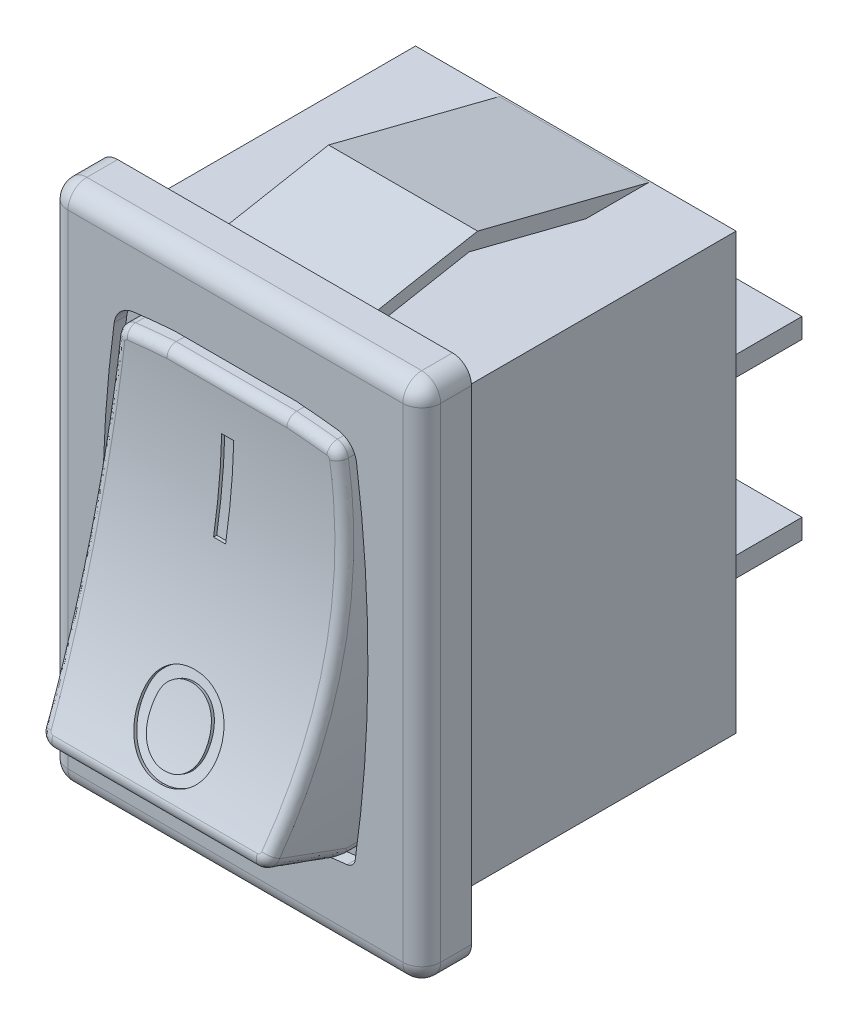
SolidWorks part; units mm, degrees
material "PW100:Mi:0:30:C1:0:1:2:Re:16:"
ref_plane "Plane1" through (0, 0, 0) normal (0, 0, 1) x (1, 0, 0)
ref_plane "Plane2" through (0, 0, 0) normal (0, 1, 0) x (1, 0, 0)
ref_plane "Plane3" through (0, 0, 0) normal (1, 0, 0) x (0, 0, -1)
sketch "Sketch1" plane through (0, 0, 0) normal (0, 0, 1) x (1, 0, 0)
  line L4 (-7.5, 10.5) -> (7.5, 10.5)
  line L5 (-7.5, 10.5) -> (-7.5, -10.5)
  line L6 (7.5, -10.5) -> (-7.5, -10.5)
  line L7 (7.5, -10.5) -> (7.5, 10.5)
  point P0 (0, 10.5)
  dimension "D1" = 15
  dimension "D2" = 21
  dimension "D3" = 7.5
  dimension "D4" = 10.5
extrude "Base-Extrude" add sketch "Sketch1" against normal blind 2
sketch "Sketch2" plane through (0, 0, -2) normal (0, 0, -1) x (-1, 0, 0)
  line L0 (-6.45, 8.75) -> (6.45, 8.75)
  line L1 (-6.45, 8.75) -> (-6.45, -8.75)
  line L2 (6.45, -8.75) -> (-6.45, -8.75)
  line L3 (6.45, -8.75) -> (6.45, 8.75)
  line L4 (0, -10.5) -> (0, 11.0998) construction
  line L5 (-7.5, -10.5) -> (7.5, -10.5) construction
  line L6 (7.5, 10.5) -> (-7.5, 10.5) construction
  dimension "D1" = 6.45
  dimension "D2" = 6.45
  dimension "D3" = 17.5
  dimension "D4" = 1.75
extrude "Boss-Extrude1" add sketch "Sketch2" along normal blind 11.7
ref_plane "Plane4" through (2.5527, 0, 0) normal (1, 0, 0) x (0, 0, -1)
ref_plane "Plane5" through (-1.8923, 0, 0) normal (1, 0, 0) x (0, 0, -1)
sketch "Sketch4" plane through (0, 0, 0) normal (1, 0, 0) x (0, 0, -1)
  line L0 (13.7, 8.75) -> (2, 8.75) construction
  line L1 (2, 10.5) -> (0, 10.5) construction
  line L2 (13.6292, 8.75) -> (6.7498, 10.5)
  line L3 (6.7498, 10.5) -> (2, 9.6175)
  line L4 (2, -10.5) -> (2, 10.5) construction
  line L5 (2, 9.6175) -> (2, 9.1271)
  line L6 (13.6292, 8.75) -> (11.1127, 8.75)
  line L8 (11.1127, 8.75) -> (6.4096, 9.9464)
  line L9 (6.4096, 9.9464) -> (2, 9.1271)
  dimension "D1" = 11.6292
  dimension "D2" = 4.7498
extrude "Boss-Extrude2" add sketch "Sketch4" against normal mid plane 6
mirror "Mirror2" about plane through (0, 0, 0) normal (0, 1, 0) of "Boss-Extrude2"
sketch "Sketch5" plane through (0, 0, 0) normal (0, 0, 1) x (1, 0, 0)
  line L0 (4.953, -7.3787) -> (4.953, 7.3787) construction
  line L1 (4.953, 0) -> (-4.953, 0) construction
  line L2 (4.953, 7.3787) -> (-4.953, 7.3787) construction
  line L3 (4.953, -7.3787) -> (-4.953, -7.3787) construction
  line L4 (-4.953, 7.3787) -> (-4.953, -7.3787) construction
  line L5 (0, 7.3787) -> (0, -7.3787) construction
  arc A0 (-4.4449, 7.079) -> (4.4449, 7.079) centre (0, -25.7343) cw
  arc A1 (-4.4449, -7.079) -> (4.4449, -7.079) centre (0, 25.7343) ccw
  arc A2 (4.4449, 7.079) -> (4.4449, -7.079) centre (-44.6187, 0) cw
  arc A3 (-4.4449, 7.079) -> (-4.4449, -7.079) centre (44.6187, 0) ccw
  dimension "D1" = 14.7574
  dimension "D2" = 9.906
extrude "Boss-Extrude3" add sketch "Sketch5" along normal blind 3.5052
ref_plane "Plane6" through (0, 0, 0) normal (1, 0, 0) x (0, 0, -1)
sketch "Sketch6" plane through (0, 0, 0) normal (1, 0, 0) x (0, 0, -1)
  line L0 (0, -7.366) -> (-3.429, -6.0242)
  line L1 (0, -10.5) -> (0, 10.5) construction
  line L3 (-0.3556, 7.2898) -> (0, 7.2898)
  line L4 (0, 7.2898) -> (0, 7.3787)
  line L5 (0, 7.3787) -> (-3.5052, 7.3787)
  line L6 (-3.5052, 7.079) -> (-3.5052, -7.079) construction
  line L7 (-3.5052, -7.3787) -> (0, -7.3787)
  line L8 (0, -7.3787) -> (0, -7.366)
  line L9 (-3.5052, 7.3787) -> (-3.5052, -7.3787)
  line L12 (-3.5052, -7.3787) -> (0, -7.3787) construction
  line L13 (0, 7.3787) -> (-3.5052, 7.3787) construction
  arc A0 (-3.429, -6.0242) -> (-0.3556, 7.2898) centre (-25.1635, 6.0047) ccw
  dimension "D1" = 24.8412
extrude "Cut-Extrude9" cut sketch "Sketch6" along normal up to surface and the other way up to surface
fillet "Fillet10" radius 0.762 8 edges at (0, 10.5, 0) (7.5, 0, 0) (0, -10.5, 0) (-7.5, 0, 0) (-7.5, 10.5, -1) (7.5, 10.5, -1) (7.5, -10.5, -1) (-7.5, -10.5, -1)
fillet "Fillet12" radius 0.508 10 edges at (4.4449, -7.079, 0.3667) (-4.4449, -7.079, 0.3667) (-2.6848, -7.2697, 0.2462) (-4.4449, 7.079, 0.1728) (4.4449, 7.079, 0.1728) (4.5181, -6.552, 2.0802) (4.9401, 1.1295, 0.8054) (-4.9522, -0.2731, 1.1287) (-4.5181, -6.552, 2.0802)
sketch "Sketch15" plane through (0, 0, 0) normal (0, 0, 1) x (1, 0, 0)
  line L0 (2.4387, 7.6708) -> (-2.4387, 7.6708)
  line L1 (-0.9223, -7.747) -> (0.9223, -7.747)
  line L2 (-0.917, -7.366) -> (0.917, -7.366)
  line L3 (-0.917, -7.366) -> (0.917, -7.366)
  line L4 (2.4248, 7.2898) -> (-2.4248, 7.2898)
  line L5 (2.4248, 7.2898) -> (-2.4248, 7.2898)
  arc A0 (-4.8765, 6.745) -> (-4.822, -7.1334) centre (44.6187, 0) ccw
  arc A1 (-4.1046, 7.5072) -> (-4.8765, 6.745) centre (-3.9957, 6.6249) ccw
  arc A2 (-2.4387, 7.6708) -> (-4.1046, 7.5072) centre (0, -25.7343) ccw
  arc A3 (4.1046, 7.5072) -> (2.4387, 7.6708) centre (0, -25.7343) ccw
  arc A4 (4.8765, 6.745) -> (4.1046, 7.5072) centre (3.9957, 6.6249) ccw
  arc A5 (4.822, -7.1334) -> (4.8765, 6.745) centre (-44.6187, 0) ccw
  arc A6 (0.9223, -7.747) -> (4.4961, -7.4566) centre (0, 25.7343) ccw
  arc A7 (-4.4961, -7.4566) -> (-0.9223, -7.747) centre (0, 25.7343) ccw
  arc A8 (0.917, -7.366) -> (4.4092, -7.0838) centre (0, 25.7343) ccw
  arc A9 (4.822, -7.1334) -> (4.4961, -7.4566) centre (4.4449, -7.079) cw
  arc A10 (-4.822, -7.1334) -> (-4.4961, -7.4566) centre (-4.4449, -7.079) ccw
  arc A12 (-2.4248, 7.2898) -> (-4.0579, 7.1291) centre (0, -25.7343) ccw
  arc A14 (4.499, 6.6935) -> (4.0579, 7.1291) centre (3.9957, 6.6249) ccw
  arc A15 (4.4717, -6.8911) -> (4.499, 6.6935) centre (-44.6187, 0) ccw
  arc A16 (0.917, -7.366) -> (4.4092, -7.0838) centre (0, 25.7343) ccw
  arc A20 (-2.4248, 7.2898) -> (-4.0579, 7.1291) centre (0, -25.7343) ccw
  arc A22 (4.499, 6.6935) -> (4.0579, 7.1291) centre (3.9957, 6.6249) ccw
  arc A23 (4.4717, -6.8911) -> (4.499, 6.6935) centre (-44.6187, 0) ccw
  arc A26 (-4.4092, -7.0838) -> (-0.917, -7.366) centre (0, 25.7343) ccw
  arc A27 (-4.4092, -7.0838) -> (-0.917, -7.366) centre (0, 25.7343) ccw
  arc A28 (-4.499, 6.6935) -> (-4.4717, -6.8911) centre (44.6187, 0) ccw
  arc A29 (-4.499, 6.6935) -> (-4.4717, -6.8911) centre (44.6187, 0) ccw
  arc A30 (-4.0579, 7.1291) -> (-4.499, 6.6935) centre (-3.9957, 6.6249) ccw
  arc A31 (-4.0579, 7.1291) -> (-4.499, 6.6935) centre (-3.9957, 6.6249) ccw
  arc A32 (4.0579, 7.1291) -> (2.4248, 7.2898) centre (0, -25.7343) ccw
  arc A33 (4.0579, 7.1291) -> (2.4248, 7.2898) centre (0, -25.7343) ccw
  spline S2 degree 3 poles (-4.4717, -6.8911) (-4.4622, -6.959) (-4.4414, -7.0233) (-4.4092, -7.0838) knots 0 0 0 0 1 1 1 1
  spline S3 degree 3 poles (-4.4717, -6.8911) (-4.4622, -6.959) (-4.4414, -7.0233) (-4.4092, -7.0838) knots 0 0 0 0 1 1 1 1
  spline S4 degree 3 poles (4.4092, -7.0838) (4.4414, -7.0233) (4.4622, -6.959) (4.4717, -6.8911) knots 0 0 0 0 1 1 1 1
  spline S5 degree 3 poles (4.4092, -7.0838) (4.4414, -7.0233) (4.4622, -6.959) (4.4717, -6.8911) knots 0 0 0 0 1 1 1 1
  dimension "D3" = 0.381
  dimension "D1" = 0
  dimension "D2" = 0.381
extrude "Cut-Extrude10" cut sketch "Sketch15" against normal blind 0.508
fillet "Fillet13" radius 0.381 12 edges at (0, -6.0242, 3.429) (-4.0633, -6.5812, 2.0056) (-4.9522, -0.2731, 1.1287) (4.9401, 1.1295, 0.8054) (4.3458, 6.993, 0.342) (-4.3591, 6.9799, 0.3415) (-4.4896, -5.8918, 3.3563) (4.4446, -5.9276, 3.3758) (0, 7.2898, 0.3556)
ref_plane "Plane7" through (0, 0, 3.175) normal (0, 0, 1) x (1, 0, 0)
sketch "Sketch17" plane through (0, 0, 3.175) normal (0, 0, 1) x (1, 0, 0)
  text T0 "I"
extrude "Cut-Extrude15" cut sketch "Sketch17" against normal offset from surface (2.9716 mm away) 0.127
ref_plane "Plane8" through (0, 1.1391, 3.1297) normal (0, 0.342, 0.9397) x (1, 0, 0)
sketch "Sketch18" plane through (0, 1.1391, 3.1297) normal (0, 0.342, 0.9397) x (1, 0, 0)
  text T0 "O"
extrude "Cut-Extrude17" cut sketch "Sketch18" against normal offset from surface (2.5638 mm away) 0.127
sketch "Sketch19" plane through (0, 0, 0) normal (0, 1, 0) x (1, 0, 0)
  line L0 (0, 13.6292) -> (0, 32.9067) construction
  line L1 (-3, 13.6292) -> (3, 13.6292) construction
  line L2 (-3.3093, 18) -> (16.6235, 18) construction
  line L3 (-0.6, 13.7) -> (-0.6, 17.1)
  line L4 (0.9, 18.6) -> (12.6, 18.6)
  line L5 (6.45, 13.7) -> (-6.45, 13.7) construction
  line L6 (0.6, 13.7) -> (0.6, 17.1)
  line L7 (12.6, 18.6) -> (12.6, 17.4)
  line L8 (0.9, 17.4) -> (12.6, 17.4)
  line L9 (0.6, 13.7) -> (-0.6, 13.7)
  line L10 (6.45, 2) -> (-6.45, 2) construction
  arc A0 (0.9, 18.6) -> (-0.6, 17.1) centre (0.9, 17.1) ccw
  arc A1 (0.9, 17.4) -> (0.6, 17.1) centre (0.9, 17.1) ccw
  dimension "D7" = 1.5
  dimension "D8" = 0.3
  dimension "D1" = 1.2
  dimension "D2" = 0.6
  dimension "D3" = 1.2
  dimension "D4" = 0.6
  dimension "D5" = 16
  dimension "D6" = 12.6
sketch "Sketch20" plane through (0, 0, 0) normal (0, 1, 0) x (1, 0, 0)
  line L0 (0, 0) -> (0, 25.703) construction
  line L1 (6.45, 13.7) -> (-6.45, 13.7) construction
  line L2 (2.4, 13.7) -> (-2.4, 13.7)
  line L3 (-2.4, 13.7) -> (-2.4, 20.7)
  line L4 (2.4, 13.7) -> (2.4, 20.7)
  line L5 (-2.4, 20.7) -> (2.4, 20.7)
  dimension "D1" = 7
  dimension "D2" = 4.8
extrude "Extrude2" add sketch "Sketch20" along normal mid plane 0.8
pattern_linear "LPattern2" count 2 spacing 7 along (0, -1, 0) of "Extrude2"
chamfer "Chamfer1" distance 0.3 angle 45 8 edges at (-2.4, 0, -20.7) (0, 0.4, -20.7) (2.4, 0, -20.7) (0, -0.4, -20.7) (-2.4, -7, -20.7) (0, -6.6, -20.7) (2.4, -7, -20.7) (0, -7.4, -20.7)
sketch "Sketch21" plane through (0, -7.4, 0) normal (0, -1, 0) x (1, 0, 0)
  line L0 (2.1, -20.7) -> (-2.1, -20.7) construction
  circle A0 centre (0, -18.2) radius 0.8
  dimension "D1" = 1.6
  dimension "D2" = 2.5
extrude "Cut-Extrude18" cut sketch "Sketch21" against normal through all
sketch "Sketch22" [suppressed] plane through (0, 0, 0) normal (0, 1, 0) x (1, 0, 0)
  line L0 (0, 13.7) -> (0, 16.4543) construction
  line L1 (6.45, 13.7) -> (-6.45, 13.7) construction
  line L2 (-1.112, 13.7) -> (-1.112, 16.3861)
  line L3 (1.112, 13.7) -> (1.112, 16.3861)
  line L4 (1.112, 13.7) -> (-1.112, 13.7)
  line L5 (-0.6388, 16.0876) -> (-0.6388, 14.6562)
  line L6 (0.6388, 16.0876) -> (0.6388, 14.6562)
  line L7 (-0.6388, 15.3719) -> (0.6388, 15.3719) construction
  arc A0 (-1.112, 16.3861) -> (1.112, 16.3861) centre (0, 14.5735) cw
  arc A1 (-0.6388, 16.0876) -> (0.6388, 16.0876) centre (0, 15.1707) cw
  arc A2 (-0.6388, 14.6562) -> (0.6388, 14.6562) centre (0, 15.5731) ccw
  dimension "D1" = 3
  dimension "D2" = 2.224
